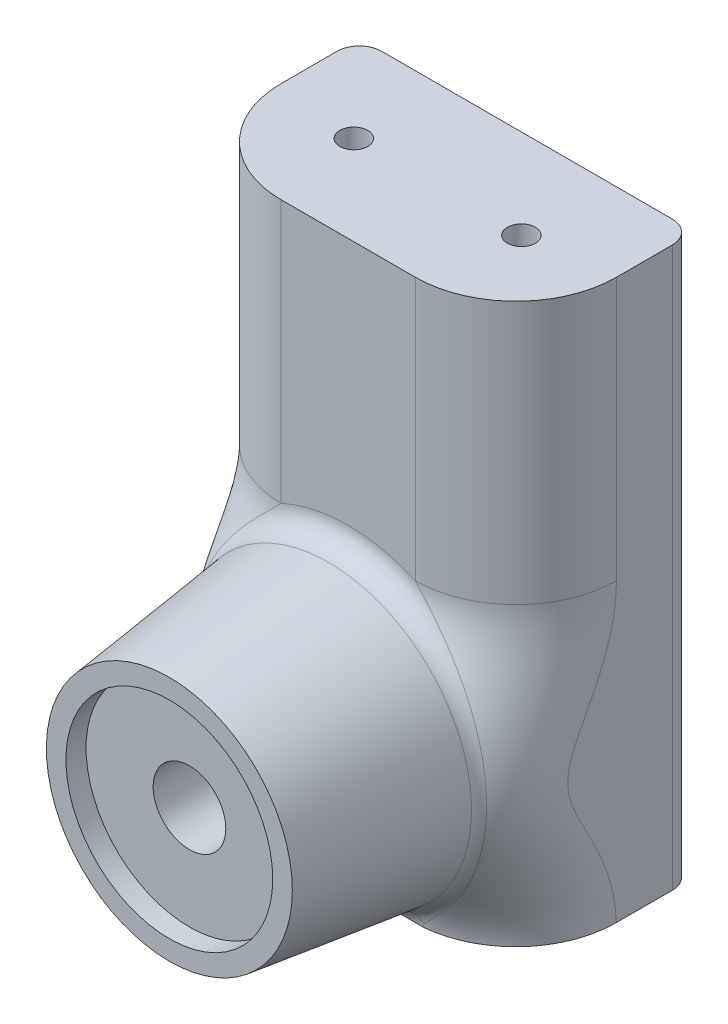
SolidWorks part; units mm, degrees
ref_plane "Спереди" through (0, 0, 0) normal (0, 0, 1) x (1, 0, 0)
ref_plane "Сверху" through (0, 0, 0) normal (0, 1, 0) x (1, 0, 0)
ref_plane "Справа" through (0, 0, 0) normal (1, 0, 0) x (0, 0, -1)
sketch "Эскиз1" plane through (0, 0, 0) normal (0, 0, 1) x (1, 0, 0)
  line L0 (0, 37) -> (0, -13) construction
  line L1 (-15, 37) -> (15, 37)
  line L2 (-15, 37) -> (-15, -13)
  line L3 (-15, -13) -> (15, -13)
  line L4 (15, 37) -> (15, -13)
  line L6 (-15, 0) -> (15, 0) construction
  dimension "D1" = 30
  dimension "D2" = 37
  dimension "D3" = 13
extrude "тело" add sketch "Эскиз1" against normal blind 16
sketch "Эскиз2" plane through (0, 0, 0) normal (0, 0, 1) x (1, 0, 0)
  circle A0 centre (0, 0) radius 11
  dimension "D1" = 22
extrude "утолщение оси" add sketch "Эскиз2" along normal blind 16
sketch "Эскиз4" plane through (0, 0, 16) normal (0, 0, 1) x (1, 0, 0)
  circle A0 centre (0, 0) radius 3.25
  dimension "D1" = 6.5
extrude "ось вращения" cut sketch "Эскиз4" against normal through all
sketch "Эскиз8" plane through (0, 0, 16) normal (0, 0, 1) x (1, 0, 0)
  circle A0 centre (0, 0) radius 9.25
  dimension "D1" = 18.5
extrude "углубление под шайбу" cut sketch "Эскиз8" against normal blind 1.8
sketch "Эскиз9" plane through (0, 0, -16) normal (0, 0, -1) x (-1, 0, 0)
  circle A0 centre (0, 0) radius 9.25
  circle A1 centre (0, 0) radius 9.25 construction
extrude "углубление под шайбу сзади" cut sketch "Эскиз9" against normal blind 1.8
chamfer "Фаска2" distance 2 distance2 16 1 edges at (11, 0, 0) first distance on face at (11, 0, 0)
fillet "Скругление5" radius 2 1 edges at (13, 0, 0)
sketch "Эскиз7" plane through (0, 37, 0) normal (0, 1, 0) x (1, 0, 0)
  line L0 (-15, 8) -> (15, 8) construction
  line L1 (-15, 16) -> (-15, 0) construction
  line L2 (15, 16) -> (15, 0) construction
  line L3 (0, 16) -> (0, 0) construction
  line L4 (15, 16) -> (-15, 16) construction
  circle A0 centre (-7.5, 8) radius 1.25
  circle A1 centre (7.5, 8) radius 1.25
  dimension "D1" = 2.5
  dimension "D2" = 15
extrude "Отверстия для шурупов снизу" cut sketch "Эскиз7" against normal blind 12
sketch "Эскиз10" plane through (0, -13, 0) normal (0, -1, 0) x (1, 0, 0)
  line L0 (14.7656, 0) -> (-14.7656, 0) construction
  circle A0 centre (-7.5, -8) radius 1.25
  circle A1 centre (7.5, -8) radius 1.25
  dimension "D1" = 8
  dimension "D2" = 2.5
extrude "Отверстия для шурупов сверху" cut sketch "Эскиз10" against normal blind 12
fillet "Скругление7" radius 2 2 edges at (15, 12, -16) (-15, 12, -16)
fillet "Скругление8" radius 9 2 edges at (15, 12, 0) (-15, 12, 0)
